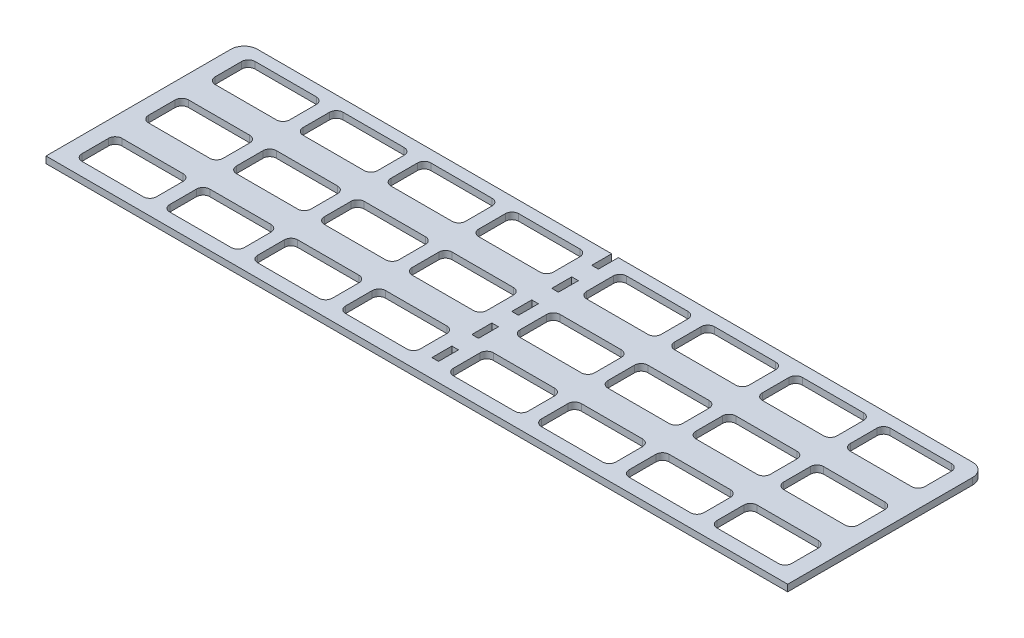
SolidWorks part; units mm, degrees
material "Balsa"
ref_plane "Front Plane" through (0, 0, 0) normal (0, 0, 1) x (1, 0, 0)
ref_plane "Top Plane" through (0, 0, 0) normal (0, 1, 0) x (1, 0, 0)
ref_plane "Right Plane" through (0, 0, 0) normal (1, 0, 0) x (0, 0, -1)
sketch "Sketch1" plane through (0, 0, 0) normal (0, 1, 0) x (1, 0, 0)
  line L0 (0, 0) -> (350.52, 0)
  line L1 (337.82, 188.976) -> (0, 188.976)
  line L3 (350.52, 0) -> (350.52, 176.276)
  line L4 (0, 188.976) -> (0, 169.926)
  line L5 (0, 169.926) -> (-3.175, 169.926)
  line L6 (-3.175, 169.926) -> (-3.175, 150.876)
  line L7 (-3.175, 150.876) -> (0, 150.876)
  line L8 (0, 150.876) -> (0, 131.826)
  line L9 (0, 131.826) -> (-3.175, 131.826)
  line L10 (-3.175, 131.826) -> (-3.175, 112.776)
  line L11 (-3.175, 112.776) -> (0, 112.776)
  line L12 (0, 112.776) -> (0, 93.726)
  line L13 (0, 93.726) -> (-3.175, 93.726)
  line L14 (-3.175, 93.726) -> (-3.175, 74.676)
  line L15 (-3.175, 74.676) -> (0, 74.676)
  line L16 (0, 74.676) -> (0, 55.626)
  line L17 (0, 55.626) -> (-3.175, 55.626)
  line L18 (-3.175, 55.626) -> (-3.175, 36.576)
  line L19 (-3.175, 36.576) -> (0, 36.576)
  line L20 (0, 36.576) -> (0, 17.526)
  line L21 (0, 17.526) -> (-3.175, 17.526)
  line L22 (-3.175, 17.526) -> (-3.175, 0)
  line L23 (-3.175, 0) -> (0, 0)
  arc A0 (337.82, 188.976) -> (350.52, 176.276) centre (337.82, 176.276) cw
  point P7 (350.52, 188.976)
  dimension "D4" = 12.7
  dimension "D2" = 350.52
  dimension "D3" = 188.976
  dimension "D5" = 19.05
  dimension "D6" = 19.05
  dimension "D7" = 3.175
  dimension "D8" = 19.05
  dimension "D9" = 19.05
  dimension "D10" = 19.05
  dimension "D11" = 19.05
  dimension "D12" = 19.05
  dimension "D13" = 19.05
  dimension "D14" = 3.175
  dimension "D15" = 3.175
  dimension "D16" = 3.175
  dimension "D17" = 3.175
  dimension "D18" = 337.82
  dimension "D19" = 3.175
  dimension "D20" = 19.05
  dimension "D21" = 3.175
  dimension "D22" = 176.276
  dimension "D23" = 3.175
extrude "Boss-Extrude1" add sketch "Sketch1" along normal blind 6.35
sketch "Sketch2" plane through (0, 6.35, 0) normal (0, 1, 0) x (1, 0, 0)
  line L68 (264.16, 19.05) -> (264.16, 44.45)
  line L69 (270.51, 12.7) -> (328.93, 12.7)
  line L70 (335.28, 19.05) -> (335.28, 44.45)
  line L71 (270.51, 50.8) -> (328.93, 50.8)
  line L72 (264.16, 82.55) -> (264.16, 107.95)
  line L73 (270.51, 76.2) -> (328.93, 76.2)
  line L74 (335.28, 82.55) -> (335.28, 107.95)
  line L76 (96.52, 19.05) -> (96.52, 44.45)
  line L77 (270.51, 114.3) -> (328.93, 114.3)
  line L78 (264.16, 146.05) -> (264.16, 171.45)
  line L79 (270.51, 139.7) -> (328.93, 139.7)
  line L80 (335.28, 146.05) -> (335.28, 171.45)
  line L81 (270.51, 177.8) -> (328.93, 177.8)
  line L91 (19.05, 12.7) -> (77.47, 12.7)
  line L92 (12.7, 19.05) -> (12.7, 44.45)
  line L93 (19.05, 50.8) -> (77.47, 50.8)
  line L94 (83.82, 19.05) -> (83.82, 44.45)
  line L95 (102.87, 12.7) -> (161.29, 12.7)
  line L96 (167.64, 19.05) -> (167.64, 44.45)
  line L97 (102.87, 50.8) -> (161.29, 50.8)
  line L98 (180.34, 19.05) -> (180.34, 44.45)
  line L99 (186.69, 12.7) -> (245.11, 12.7)
  line L100 (251.46, 19.05) -> (251.46, 44.45)
  line L101 (186.69, 50.8) -> (245.11, 50.8)
  line L102 (96.52, 82.55) -> (96.52, 107.95)
  line L103 (102.87, 76.2) -> (161.29, 76.2)
  line L104 (167.64, 82.55) -> (167.64, 107.95)
  line L105 (102.87, 114.3) -> (161.29, 114.3)
  line L106 (180.34, 82.55) -> (180.34, 107.95)
  line L107 (186.69, 76.2) -> (245.11, 76.2)
  line L108 (251.46, 82.55) -> (251.46, 107.95)
  line L109 (186.69, 114.3) -> (245.11, 114.3)
  line L110 (96.52, 146.05) -> (96.52, 171.45)
  line L111 (102.87, 139.7) -> (161.29, 139.7)
  line L112 (167.64, 146.05) -> (167.64, 171.45)
  line L113 (102.87, 177.8) -> (161.29, 177.8)
  line L114 (180.34, 146.05) -> (180.34, 171.45)
  line L115 (186.69, 139.7) -> (245.11, 139.7)
  line L116 (251.46, 146.05) -> (251.46, 171.45)
  line L117 (186.69, 177.8) -> (245.11, 177.8)
  line L118 (12.7, 82.55) -> (12.7, 107.95)
  line L119 (19.05, 76.2) -> (77.47, 76.2)
  line L120 (83.82, 82.55) -> (83.82, 107.95)
  line L121 (19.05, 114.3) -> (77.47, 114.3)
  line L122 (12.7, 146.05) -> (12.7, 171.45)
  line L123 (19.05, 139.7) -> (77.47, 139.7)
  line L124 (83.82, 146.05) -> (83.82, 171.45)
  line L125 (19.05, 177.8) -> (77.47, 177.8)
  line L126 (12.7, 19.05) -> (12.7, 82.55) construction
  arc A0 (77.47, 12.7) -> (83.82, 19.05) centre (77.47, 19.05) ccw
  arc A1 (19.05, 12.7) -> (12.7, 19.05) centre (19.05, 19.05) cw
  arc A2 (12.7, 44.45) -> (19.05, 50.8) centre (19.05, 44.45) cw
  arc A3 (77.47, 50.8) -> (83.82, 44.45) centre (77.47, 44.45) cw
  arc A4 (96.52, 44.45) -> (102.87, 50.8) centre (102.87, 44.45) cw
  arc A5 (102.87, 12.7) -> (96.52, 19.05) centre (102.87, 19.05) cw
  arc A6 (161.29, 12.7) -> (167.64, 19.05) centre (161.29, 19.05) ccw
  arc A7 (161.29, 50.8) -> (167.64, 44.45) centre (161.29, 44.45) cw
  arc A8 (180.34, 44.45) -> (186.69, 50.8) centre (186.69, 44.45) cw
  arc A9 (186.69, 12.7) -> (180.34, 19.05) centre (186.69, 19.05) cw
  arc A10 (245.11, 12.7) -> (251.46, 19.05) centre (245.11, 19.05) ccw
  arc A11 (245.11, 50.8) -> (251.46, 44.45) centre (245.11, 44.45) cw
  arc A12 (96.52, 107.95) -> (102.87, 114.3) centre (102.87, 107.95) cw
  arc A13 (102.87, 76.2) -> (96.52, 82.55) centre (102.87, 82.55) cw
  arc A14 (161.29, 76.2) -> (167.64, 82.55) centre (161.29, 82.55) ccw
  arc A15 (161.29, 114.3) -> (167.64, 107.95) centre (161.29, 107.95) cw
  arc A16 (180.34, 107.95) -> (186.69, 114.3) centre (186.69, 107.95) cw
  arc A17 (186.69, 76.2) -> (180.34, 82.55) centre (186.69, 82.55) cw
  arc A18 (245.11, 76.2) -> (251.46, 82.55) centre (245.11, 82.55) ccw
  arc A19 (245.11, 114.3) -> (251.46, 107.95) centre (245.11, 107.95) cw
  arc A20 (96.52, 171.45) -> (102.87, 177.8) centre (102.87, 171.45) cw
  arc A21 (102.87, 139.7) -> (96.52, 146.05) centre (102.87, 146.05) cw
  arc A22 (161.29, 139.7) -> (167.64, 146.05) centre (161.29, 146.05) ccw
  arc A23 (161.29, 177.8) -> (167.64, 171.45) centre (161.29, 171.45) cw
  arc A24 (180.34, 171.45) -> (186.69, 177.8) centre (186.69, 171.45) cw
  arc A25 (186.69, 139.7) -> (180.34, 146.05) centre (186.69, 146.05) cw
  arc A26 (245.11, 139.7) -> (251.46, 146.05) centre (245.11, 146.05) ccw
  arc A27 (245.11, 177.8) -> (251.46, 171.45) centre (245.11, 171.45) cw
  arc A28 (12.7, 107.95) -> (19.05, 114.3) centre (19.05, 107.95) cw
  arc A29 (19.05, 76.2) -> (12.7, 82.55) centre (19.05, 82.55) cw
  arc A30 (77.47, 76.2) -> (83.82, 82.55) centre (77.47, 82.55) ccw
  arc A31 (77.47, 114.3) -> (83.82, 107.95) centre (77.47, 107.95) cw
  arc A32 (12.7, 171.45) -> (19.05, 177.8) centre (19.05, 171.45) cw
  arc A33 (19.05, 139.7) -> (12.7, 146.05) centre (19.05, 146.05) cw
  arc A34 (77.47, 139.7) -> (83.82, 146.05) centre (77.47, 146.05) ccw
  arc A35 (77.47, 177.8) -> (83.82, 171.45) centre (77.47, 171.45) cw
  arc A36 (264.16, 44.45) -> (270.51, 50.8) centre (270.51, 44.45) cw
  arc A37 (270.51, 12.7) -> (264.16, 19.05) centre (270.51, 19.05) cw
  arc A38 (328.93, 12.7) -> (335.28, 19.05) centre (328.93, 19.05) ccw
  arc A39 (328.93, 50.8) -> (335.28, 44.45) centre (328.93, 44.45) cw
  arc A40 (264.16, 107.95) -> (270.51, 114.3) centre (270.51, 107.95) cw
  arc A41 (270.51, 76.2) -> (264.16, 82.55) centre (270.51, 82.55) cw
  arc A42 (328.93, 76.2) -> (335.28, 82.55) centre (328.93, 82.55) ccw
  arc A43 (328.93, 114.3) -> (335.28, 107.95) centre (328.93, 107.95) cw
  arc A44 (264.16, 171.45) -> (270.51, 177.8) centre (270.51, 171.45) cw
  arc A45 (270.51, 139.7) -> (264.16, 146.05) centre (270.51, 146.05) cw
  arc A46 (328.93, 139.7) -> (335.28, 146.05) centre (328.93, 146.05) ccw
  arc A47 (328.93, 177.8) -> (335.28, 171.45) centre (328.93, 171.45) cw
  point P10 (83.82, 12.7)
  point P13 (12.7, 12.7)
  point P16 (12.7, 50.8)
  point P19 (96.52, 31.75)
  dimension "D7" = 3
  dimension "D5" = 6.35
  dimension "D2" = 71.12
  dimension "D3" = 12.7
  dimension "D4" = 38.1
  dimension "D8" = 63.5
  dimension "D9" = 25.4
  dimension "D10" = 12.7
  dimension "D11" = 12.7
  dimension "D6" = 4
extrude "Cut-Extrude1" cut sketch "Sketch2" against normal up to surface (6.35 mm away) up to face at (43.9018, 0, -97.562)
mirror "Mirror1" about plane through (-3.175, 6.35, -93.726) normal (1, 0, 0) of "Cut-Extrude1", "Boss-Extrude1"
